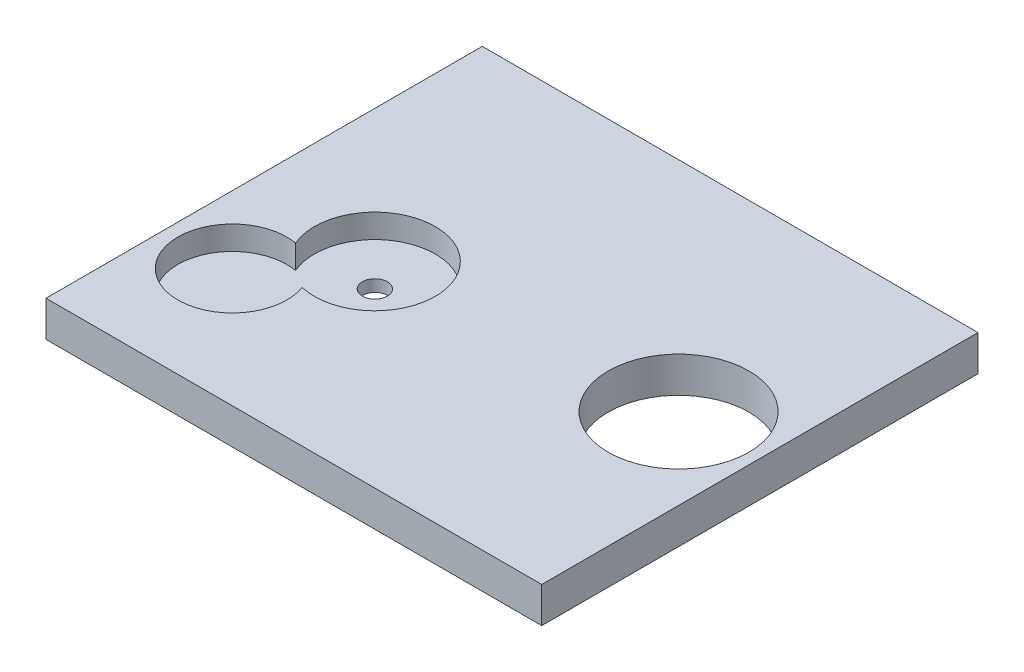
SolidWorks part; units mm, degrees
ref_plane "Front" through (0, 0, 0) normal (0, 0, 1) x (1, 0, 0)
ref_plane "Top" through (0, 0, 0) normal (0, 1, 0) x (1, 0, 0)
ref_plane "Right" through (0, 0, 0) normal (1, 0, 0) x (0, 0, -1)
sketch "Sketch1" plane through (0, 0, 0) normal (0, 1, 0) x (1, 0, 0)
  line L1 (0, 0) -> (125, 0)
  line L2 (0, 0) -> (0, 110)
  line L3 (0, 110) -> (125, 110)
  line L4 (125, 0) -> (125, 110)
  dimension "D1" = 125
  dimension "D2" = 110
extrude "Top_Base" add sketch "Sketch1" along normal blind 9
sketch "Fingers_Position" plane through (0, 9, 0) normal (0, 1, 0) x (1, 0, 0)
  line L0 (74.5, 89.5) -> (39.5, 89.5) construction
  line L1 (74.5, 73.5) -> (19.5, 73.5) construction
  line L2 (74.5, 73.5) -> (74.5, 105.5) construction
  line L3 (74.5, 105.5) -> (19.5, 105.5) construction
  line L4 (19.5, 73.5) -> (19.5, 105.5) construction
  line L5 (74.5, 4.5) -> (19.5, 4.5) construction
  line L6 (74.5, 4.5) -> (74.5, 36.5) construction
  line L7 (74.5, 36.5) -> (19.5, 36.5) construction
  line L8 (19.5, 4.5) -> (19.5, 36.5) construction
  line L10 (39.5, 20.5) -> (74.5, 20.5) construction
  line L11 (125, 110) -> (0, 110) construction
  line L12 (0, 110) -> (0, 0) construction
  point P10 (0, 0)
  point P17 (46.7297, 89.5)
  point P18 (41.9077, 89.5)
  dimension "D1" = 55
  dimension "D2" = 32
  dimension "D3" = 69
  dimension "D4" = 4.5
  dimension "D5" = 19.5
  dimension "D6" = 20
sketch "Intermediate_Gear_Position" plane through (0, 9, 0) normal (0, 1, 0) x (1, 0, 0)
  line L0 (0, 49.485) -> (33.4314, 49.485) construction
  line L1 (0, 110) -> (0, 0) construction
  line L2 (33.4314, 49.485) -> (33.4314, 110) construction
  line L3 (125, 110) -> (0, 110) construction
  line L4 (33.4314, 49.485) -> (33.4314, 0) construction
  line L5 (0, 0) -> (125, 0) construction
  circle A0 centre (33.4314, 49.485) radius 15 construction
  circle A1 centre (33.4314, 49.485) radius 13.5
  dimension "D3" = 30
  dimension "D4" = 27
  dimension "D1" = 33.4314
  dimension "D2" = 49.485
sketch "Drive_Gear_Position" plane through (0, 9, 0) normal (0, 1, 0) x (1, 0, 0)
  line L0 (5, 20.9848) -> (29, 20.9848) construction
  line L1 (5, 38.9848) -> (29, 38.9848)
  line L2 (5, 38.9848) -> (5, 2.9848)
  line L3 (5, 2.9848) -> (29, 2.9848)
  line L4 (29, 38.9848) -> (29, 2.9848)
  line L5 (17, 38.9848) -> (17, 2.9848) construction
  line L6 (95.5, 98) -> (95.5, 43) construction
  line L7 (79.5, 98) -> (111.5, 98) construction
  line L8 (79.5, 98) -> (79.5, 43) construction
  line L9 (79.5, 43) -> (111.5, 43) construction
  line L10 (111.5, 98) -> (111.5, 43) construction
  line L11 (77.5, 67) -> (113.5, 67) construction
  line L12 (77.5, 67) -> (77.5, 43) construction
  line L13 (77.5, 43) -> (113.5, 43) construction
  line L14 (113.5, 67) -> (113.5, 43) construction
  line L15 (95.5, 67) -> (95.5, 43) construction
  line L17 (125, 0) -> (125, 110) construction
  line L18 (125, 110) -> (0, 110) construction
  line L20 (0, 110) -> (0, 0) construction
  circle A0 centre (17, 29.9848) radius 9 construction
  circle A1 centre (17, 29.9848) radius 13.5 construction
  circle A2 centre (17, 29.9848) radius 12
  circle A3 centre (33.4314, 49.485) radius 13.5 construction
  point P29 (62.1945, 58.2814)
  point P30 (61.7563, 55.4844)
  point P31 (0, 0)
  point P32 (13.4421, 50.6428)
  point P33 (0, 0)
  point P34 (0, 0)
  point P35 (14.1402, 72.4773)
  point P36 (19.5, 43)
  point P37 (11.5129, 63.9413)
  point P38 (15.1145, 47.4427)
  point P39 (0, 0)
  point P40 (16.8929, 30.0756)
  dimension "D1" = 27
  dimension "D2" = 18
  dimension "D5" = 24
  dimension "D3" = 24
  dimension "D4" = 36
  dimension "D6" = 32
  dimension "D7" = 55
  dimension "D8" = 24
  dimension "D9" = 36
  dimension "D10" = 13.5
  dimension "D11" = 12
  dimension "D12" = 5
sketch "Sketch5" plane through (0, 9, 0) normal (0, 1, 0) x (1, 0, 0)
  circle A0 centre (33.4314, 49.485) radius 15.25
  circle A1 centre (17, 29.9848) radius 13.75
  dimension "D1" = 27.5
  dimension "D2" = 30.5
extrude "Gears_Extrude_Cut" cut sketch "Sketch5" against normal blind 6 contours A0 A1 | A1 A0 | A0 A1 region at (33.8381, 9, -49.9676) region at (24.7204, 9, -39.1471) region at (16.5519, 9, -29.453)
sketch "Sketch7" plane through (0, 9, 0) normal (0, 1, 0) x (1, 0, 0)
  circle A0 centre (33.4314, 49.485) radius 3.15
  dimension "D1" = 6.3
extrude "Key_Extrude_Cut" cut sketch "Sketch7" against normal through all
sketch "Sketch8" plane through (0, 9, 0) normal (0, 1, 0) x (1, 0, 0)
  line L0 (113.5, 55) -> (77.5, 55) construction
  line L1 (113.5, 67) -> (113.5, 43) construction
  line L2 (77.5, 67) -> (77.5, 43) construction
  circle A0 centre (104.5, 55) radius 9 construction
  circle A1 centre (104.5, 55) radius 17.75
  dimension "D1" = 18
  dimension "D2" = 35.5
extrude "Cut-Extrude3" cut sketch "Sketch8" against normal through all
